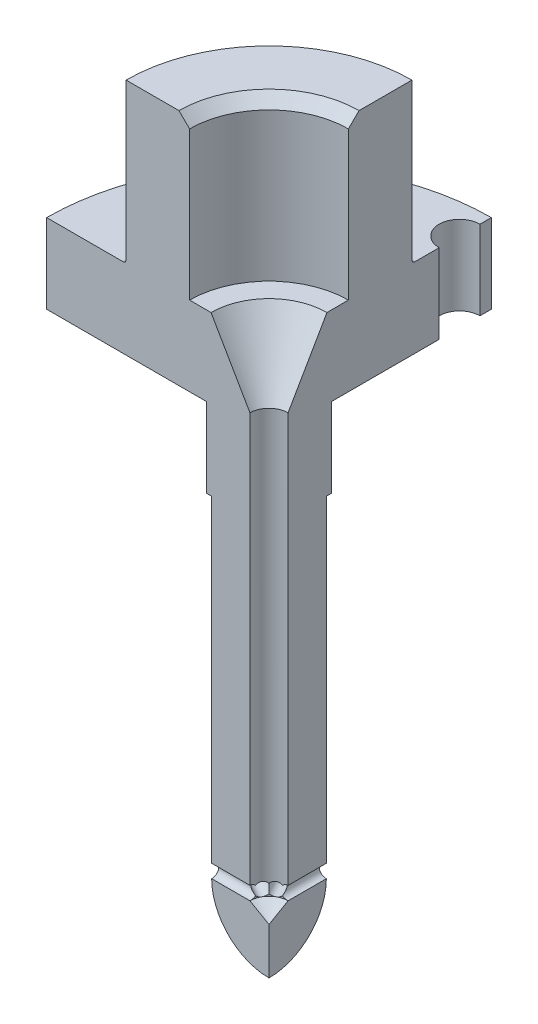
SolidWorks part; units mm, degrees
note: '?' marks a value the reader was unsure of.
ref_plane "Front Plane" through (0, 0, 0) normal (0, 0, 1) x (1, 0, 0)
ref_plane "Top Plane" through (0, 0, 0) normal (0, 1, 0) x (1, 0, 0)
ref_plane "Right Plane" through (0, 0, 0) normal (1, 0, 0) x (0, 0, -1)
sketch "Sketch1" plane through (0, 0, 0) normal (0, 0, 1) x (1, 0, 0)
  line L0 (-4.5847, -3.4083) -> (-1.524, -3.4083)
  line L1 (0, 8.2157) -> (0, -2.0672) construction
  line L2 (-4.5847, 23.0788) -> (-1.524, 23.0788)
  line L3 (-4.5847, -3.4083) -> (-4.5847, 23.0788)
  line L7 (-1.524, 23.0788) -> (-1.524, -3.4083)
  dimension "D2" = 4.5847
  dimension "D3" = 1.524
  dimension "D4" = 26.4871
revolve "Revolve2" add sketch "Sketch1" angle 360 about L1
ref_plane "Plane1" through (-4.5847, 0, 0) normal (-1, 0, 0) x (0, 0, 1)
ref_axis "Axis2" through (0, -3.4083, 0) along (0, 1, 0)?
ref_plane "Plane2" through (0, 23.0788, 0) normal (0, -1, 0) x (-1, 0, 0)
sketch "Sketch3" plane through (0, 23.0788, 0) normal (0, -1, 0) x (-1, 0, 0)
  circle A0 centre (0, 0) radius 1.524 construction
  circle A1 centre (0, 0) radius 4.5847 construction
  circle A2 centre (0, 0) radius 1.524
  circle A3 centre (0, 0) radius 4.5847
extrude "Boss-Extrude1" add sketch "Sketch3" against normal blind 6.35
ref_plane "Plane3" through (0, 29.4288, 0) normal (0, 1, 0) x (1, 0, 0)
sketch "Sketch4" plane through (0, 29.4288, 0) normal (0, 1, 0) x (1, 0, 0)
  circle A0 centre (0, 0) radius 17.78
  circle A1 centre (0, 0) radius 1.524
  dimension "D2" = 17.78
  dimension "D1" = 3.048
extrude "Boss-Extrude2" add sketch "Sketch4" along normal blind 6.35
sketch "Sketch11" plane through (0, 35.7788, 0) normal (0, 1, 0) x (1, 0, 0)
  line L0 (0, 0) -> (0, -15.24) construction
  circle A0 centre (0, -15.24) radius 1.6319
  circle A1 centre (0, 0) radius 15.24 construction
  dimension "D2" = 3.2639
extrude "Cut-Extrude2" cut sketch "Sketch11" against normal up to next
ref_axis "Axis1" through (0, -3.4083, 0) along (0, 1, 0)?
pattern_circular "CirPattern2" count 6 over 360 about axis through (0, 0, 0) along (0, 1, 0) of "Cut-Extrude2"
chamfer "Chamfer1" distance 3.1128 angle 60 1 edges at (0, 35.7788, 1.524) first distance on face at (-14.6115, 35.7788, 8.436)
sketch "Sketch13" plane through (0, 35.7788, 0) normal (0, 1, 0) x (1, 0, 0)
  circle A0 centre (0, 0) radius 6.35
  circle A1 centre (0, 0) radius 11.43
extrude "Boss-Extrude4" add sketch "Sketch13" along normal blind 12.7
fillet "Fillet4" radius 0.254 1 edges at (0, 35.7788, 11.43)
chamfer "Chamfer2" distance 0.8517 distance2 0.8395 1 edges at (0, 48.4788, 6.35) first distance on face at (0, 48.4788, 11.43)
sketch "Sketch14" plane through (0, 35.7788, 0) normal (0, 1, 0) x (1, 0, 0)
  circle A0 centre (-13.1982, -7.62) radius 2.794
sketch "Sketch15" plane through (0, 29.4288, 0) normal (0, -1, 0) x (1, 0, 0)
  circle A0 centre (0, 0) radius 5
  circle A1 centre (0, 0) radius 3.556
extrude "Boss-Extrude5" add sketch "Sketch15" along normal blind 6.35
sketch "Sketch18" plane through (0, -3.4083, 0) normal (0, -1, 0) x (1, 0, 0)
  circle A0 centre (0, 0) radius 4.318
sketch "Sketch19" plane through (0, 0, 0) normal (0, 0, 1) x (1, 0, 0)
  line L0 (0, -3.4083) -> (-4.5847, -3.4083)
  line L1 (-4.318, -3.4083) -> (4.318, -3.4083) construction
  line L2 (0, -3.4083) -> (0, -7.993)
  arc A0 (-4.5847, -3.4083) -> (0, -7.993) centre (0, -3.4083) ccw
  dimension "D2" = 4.5847
  dimension "D1" = 4.5847
ref_axis "Axis3" through (0, -3.4083, 0) along (0, -1, 0)
revolve "Revolve4" add sketch "Sketch19" angle 360 about axis through (0, -3.4083, 0) along (0, -1, 0)
sketch "Sketch20" plane through (-4.5847, 0, 0) normal (-1, 0, 0) x (0, 0, 1)
  line L1 (0, -3.4083) -> (0, -7.993) construction
  line L2 (-4.318, -3.4083) -> (4.318, -3.4083) construction
  circle A0 centre (0, -2.8749) radius 0.5334
  dimension "D2" = 1.0668
extrude "Cut-Extrude3" cut sketch "Sketch20" against normal up to next
pattern_circular "CirPattern3" count 12 over 360 about axis through (0, -3.4083, 0) along (0, -1, 0) of "Cut-Extrude3"
sketch "Sketch21" plane through (0, 0, 0) normal (0, 0, 1) x (1, 0, 0)
  line L0 (0, -3.4083) -> (0, -4.2882)
  line L1 (-4.318, -3.4083) -> (4.318, -3.4083) construction
  line L5 (0, -3.4083) -> (-1.524, -3.4083)
  line L6 (-1.524, -3.4083) -> (0, -4.2882)
  spline S0 degree 2 poles (-1.4721, -3.234) (-1.493, -3.3197) (-1.524, -3.4083) knots 0.78791 0.78791 0.78791 1 1 1 weights 0.001831 0.001944 0.002057 construction
  dimension "D1" = 30
revolve "Cut-Revolve4" cut sketch "Sketch21" angle 360 about axis through (0, -3.4083, 0) along (0, -1, 0)
sketch "Sketch22" plane through (0, 48.4788, 0) normal (0, 1, 0) x (1, 0, 0)
  line L0 (0, 0) -> (0, 22.2025)
  line L1 (0, 22.2025) -> (22.6785, 22.2025)
  line L2 (22.6785, 22.2025) -> (22.6785, -24.6676)
  line L3 (22.6785, -24.6676) -> (-30.4494, -24.6676)
  line L4 (-30.4494, -24.6676) -> (-30.4494, 0)
  line L5 (-30.4494, 0) -> (0, 0)
extrude "Cut-Extrude4" cut sketch "Sketch22" against normal through all both and the other way through all
equation "\"ManifoldThickness\"= 0.250"
equation "\"D1@Boss-Extrude1\"=\"ManifoldThickness\""
equation "\"SkipDistance\"= \"OD\"'equal to pintle OD"
equation "\"OD\"= 0.361"
equation "\"AnnulusLength\"= 0.3084"
equation "\"ManifoldChamberThickness\"= 0.3314"
equation "\"D4@Sketch1\"=\"SkipDistance\"+\"AnnulusLength\"+\"ManifoldChamberThickness\"+\"HoleHeight\""
equation "\"HoleHeight\"= .0420"
equation "\"D2@Sketch1\"=\"OD\"/2"
equation "\"IR\"= 0.06"
equation "\"D3@Sketch1\" = \"IR\""
equation "\"ID\"= \"IR\" * 2"
equation "\"440loose\"= 0.1285"
equation "\"D2@Sketch11\"=\"440loose\""
equation "\"ManifoldPlateThickness\"= 0.25"
equation "\"WeldHeight\"= 0.035"
equation "\"HoleFromEnd\"= \"HoleHeight\" / 2"
equation "\"D1@Sketch20\"=\"HoleFromEnd\""
equation "\"D2@Sketch20\"=\"HoleHeight\""
equation "\"D1@Sketch19\"=\"OD\"/2"
equation "\"D1@Sketch4\"=\"ID\""
